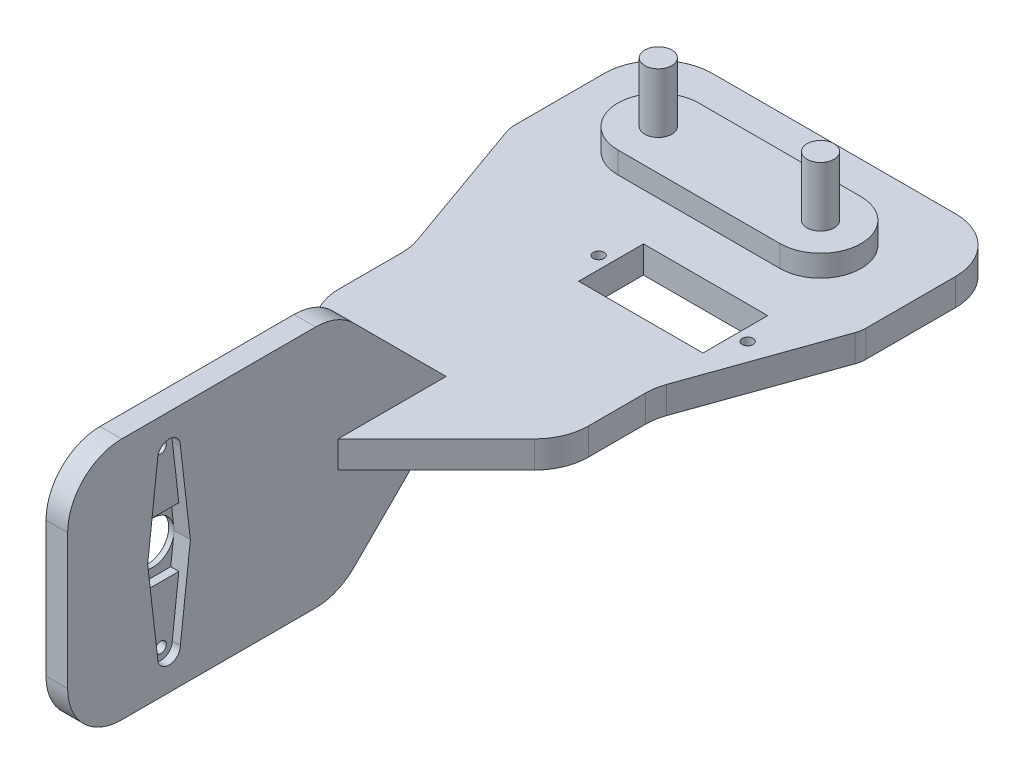
SolidWorks part; units mm, degrees
note: The reader was unsure of these and kept them because the rebuilt part matched: shared geometry of "Sketch1<3>", "Sketch1<4>", "Sketch8<3>", "Sketch8<4>".
ref_plane "Front Plane" through (0, 0, 0) normal (0, 0, 1) x (1, 0, 0)
ref_plane "Top Plane" through (0, 0, 0) normal (0, 1, 0) x (1, 0, 0)
ref_plane "Right Plane" through (0, 0, 0) normal (1, 0, 0) x (0, 0, -1)
sketch "Sketch1" plane through (0, 0, 0) normal (0, 1, 0) x (1, 0, 0)
  line L0 (15.5811, 10.6625) -> (15.5811, -11.8375) construction
  line L2 (-31.9189, 1.554) -> (-31.9189, 18.1625)
  line L3 (-21.9189, 28.1625) -> (23.0811, 28.1625)
  line L5 (10.4961, -17.4925) -> (10.4961, -5.5125) construction
  line L6 (-21.9189, -64.9925) -> (23.0811, -64.9925)
  line L7 (-0.9939, -17.4925) -> (21.9861, -17.4925)
  line L8 (-0.9939, -17.4925) -> (-0.9939, -5.5125)
  line L9 (-0.9939, -5.5125) -> (21.9861, -5.5125)
  line L11 (23.0811, -27.4925) -> (23.0811, -64.9925)
  line L17 (15.5811, 18.1625) -> (-14.4189, 18.1625)
  line L18 (-14.4189, 3.1625) -> (15.5811, 3.1625)
  line L19 (-31.6205, -0.1776) -> (-21.9189, -27.4925)
  line L23 (32.7828, -0.1776) -> (23.0811, -27.4925)
  line L24 (21.9861, -17.4925) -> (21.9861, -5.5125)
  line L25 (33.0811, 1.554) -> (33.0811, 18.1625)
  line L26 (-21.9189, -27.4925) -> (-21.9189, -64.9925)
  circle A1 centre (-3.2839, -11.5025) radius 1
  circle A3 centre (15.5811, -11.8375) radius 2.525 construction
  arc A4 (-14.4189, 18.1625) -> (-14.4189, 3.1625) centre (-14.4189, 10.6625) ccw
  circle A5 centre (-14.4189, 10.6625) radius 2.5
  arc A6 (-31.9189, 18.1625) -> (-21.9189, 28.1625) centre (-21.9189, 18.1625) cw
  arc A8 (-31.6205, -0.1776) -> (-31.9189, 1.554) centre (-26.7453, 1.554) cw
  arc A9 (32.7828, -0.1776) -> (33.0811, 1.554) centre (27.9076, 1.554) ccw
  arc A11 (33.0811, 18.1625) -> (23.0811, 28.1625) centre (23.0811, 18.1625) ccw
  circle A12 centre (15.5811, 10.6625) radius 2.5
  arc A13 (15.5811, 18.1625) -> (15.5811, 3.1625) centre (15.5811, 10.6625) cw
  circle A15 centre (15.5811, -11.8375) radius 7.5 construction
  circle A17 centre (24.2761, -11.5025) radius 1
  point P0 (0, 0)
  point P1 (32.5, 0.6625)
  point P7 (10.4961, -17.4925)
  point P17 (10.4961, -5.5125)
  point P24 (0.5811, 18.1625)
  point P37 (-31.9189, 0.6625)
  point P46 (21.9861, -11.5025)
  point P56 (0.5811, 3.1625)
  dimension "D7" = 2
  dimension "D10" = 5.05
  dimension "D6" = 5
  dimension "D8" = 5
  dimension "D19" = 10
  dimension "D20" = 8.675
  dimension "D15" = 15
  dimension "D16" = 5.1735
  dimension "D12" = 6.405
  dimension "D18" = 6.405
  dimension "D3" = 10
  dimension "D4" = 11.49
  dimension "D5" = 10
  dimension "D9" = 2.29
  dimension "D11" = 37.5
  dimension "D13" = 22.5
  dimension "D14" = 10
  dimension "D17" = 11.98
  dimension "D21" = 17.5
  dimension "D22" = 65
  dimension "D23" = 30
  dimension "D24" = 45
extrude "Boss-Extrude1" add sketch "Sketch1" along normal blind 5
extrude "Boss-Extrude2" add sketch "Sketch1<3>" along normal blind 9 contours A13 L17 A4 L18 A5 A12
sketch "Sketch1<3>" plane through (0, 0, 0) normal (0, 1, 0) x (1, 0, 0) same geometry as "Sketch1"
extrude "Boss-Extrude3" add sketch "Sketch1<4>" along normal blind 20 contours A12 | A5
sketch "Sketch1<4>" plane through (0, 0, 0) normal (0, 1, 0) x (1, 0, 0) same geometry as "Sketch1"
sketch "Sketch2" plane through (0, 0, 64.9925) normal (0, 0, 1) x (1, 0, 0)
  line L1 (-2, 25) -> (2, 25)
  line L2 (-2, 25) -> (-2, -20)
  line L3 (-2, -20) -> (2, -20)
  line L4 (2, 25) -> (2, -20)
  line L5 (-2, 25) -> (2, -20) construction
  line L6 (-2, -20) -> (2, 25) construction
  line L7 (-21.9189, 0) -> (23.0811, 0) construction
  point P0 (0, 2.5)
  dimension "D1" = 2.5
  dimension "D2" = 45
  dimension "D3" = 4
ref_plane "Plane1" through (0.5811, 0, 0) normal (-1, 0, 0) x (0, 0, 1)
ref_plane "Plane2" through (0, 2.5, 0) normal (0, 1, 0) x (1, 0, 0)
extrude "Boss-Extrude4" add sketch "Sketch2" along normal blind 50 contours L4 L3 L2 L1
sketch "Sketch6" plane through (0, 5, 0) normal (0, 1, 0) x (1, 0, 0)
  line L0 (-2, -64.9925) -> (-21.9189, -45.0736)
  line L1 (-21.9189, -27.4925) -> (-21.9189, -64.9925) construction
  line L2 (-21.9189, -64.9925) -> (-2, -64.9925) construction
  line L3 (-21.9189, -45.0736) -> (-21.9189, -64.9925)
  line L4 (-21.9189, -64.9925) -> (-2, -64.9925)
  line L5 (2, -64.9925) -> (23.0811, -43.9114)
  line L6 (23.0811, -27.4925) -> (23.0811, -64.9925) construction
  line L7 (2, -64.9925) -> (23.0811, -64.9925) construction
  line L8 (23.0811, -43.9114) -> (23.0811, -64.9925)
  line L9 (23.0811, -64.9925) -> (2, -64.9925)
  dimension "D1" = 45
  dimension "D2" = 45
extrude "Cut-Extrude1" cut sketch "Sketch6" against normal through all
ref_plane "Plane3" through (0, 0, 0) normal (1, 0, 0) x (0, 0, -1)
sketch "Sketch7" plane through (0, 0, 0) normal (1, 0, 0) x (0, 0, -1)
  line L0 (-64.9925, 25) -> (-44.9925, 5)
  line L1 (-64.9925, 25) -> (-64.9925, 5) construction
  line L2 (-64.9925, 5) -> (-45.0736, 5) construction
  dimension "D1" = 45
rib "Rib8" sketch "Sketch7" sketch "Sketch7" thickness 4 extrusion direction parallel to sketch draft on no parameters "D1"=4
mirror "Mirror2" about plane through (0, 2.5, 0) normal (0, 1, 0) of "Rib8"
sketch "Sketch8" plane through (2, 0, 0) normal (1, 0, 0) x (0, 0, -1)
  line L0 (35.75, 2.5) -> (-35.75, 2.5) construction
  line L1 (-98.3425, 18.5) -> (-100.1925, 2.5)
  line L2 (-94.1425, 18.5) -> (-92.2925, 2.5)
  line L3 (-114.9925, 25) -> (-114.9925, -20) construction
  line L4 (-64.9925, 5) -> (-64.9925, 0) construction
  line L5 (-98.3425, -13.5) -> (-100.1925, 2.5)
  line L6 (-94.1425, -13.5) -> (-92.2925, 2.5)
  line L7 (-99.5566, 8) -> (-92.9284, 8)
  line L8 (-99.5566, -3) -> (-92.9284, -3)
  arc A0 (-100.0883, 3.4014) -> (-100.0883, 1.5986) centre (-96.2425, 2.5) ccw
  arc A1 (-94.1425, 18.5) -> (-98.3425, 18.5) centre (-96.2425, 18.5) ccw
  circle A2 centre (-96.2425, 18.5) radius 1
  arc A3 (-94.1425, -13.5) -> (-98.3425, -13.5) centre (-96.2425, -13.5) cw
  circle A4 centre (-96.2425, -13.5) radius 1
  arc A5 (-92.3967, 1.5986) -> (-92.3967, 3.4014) centre (-96.2425, 2.5) ccw
  dimension "D1" = 7.9
  dimension "D2" = 4.2
  dimension "D6" = 2
  dimension "D3" = 32
  dimension "D4" = 18.75
  dimension "D5" = 50
  dimension "D7" = 11
  dimension "D8" = 5.5
extrude "Cut-Extrude2" cut sketch "Sketch8" against normal blind 3 contours A3 L6 L2 A1 L1 L5 A2 A4
extrude "Cut-Extrude3" cut sketch "Sketch8<3>" against normal through all contours A2 | A4
sketch "Sketch8<3>" plane through (2, 0, 0) normal (1, 0, 0) x (0, 0, -1) same geometry as "Sketch8"
fillet "Fillet1" radius 10 8 edges at (0, -20, 114.9925) (0, -20, 64.9925) (0, 25, 114.9925) (0, 25, 64.9925) (-21.9189, 2.5, 27.4925) (-21.9189, 2.5, 45.0736) (23.0811, 2.5, 27.4925) (23.0811, 2.5, 43.9114)
extrude "Cut-Extrude4" cut sketch "Sketch8<4>" against normal blind 1.5 contours L2 A1 L1 L7 A2 | A3 L6 L8 L5 A4
sketch "Sketch8<4>" plane through (2, 0, 0) normal (1, 0, 0) x (0, 0, -1) same geometry as "Sketch8"
sketch "Sketch9" plane through (-1, 0, 0) normal (1, 0, 0) x (0, 0, -1)
  line L0 (-99.5566, 8) -> (-92.9284, 8) construction
  circle A0 centre (-96.2425, 2.5) radius 3.95
  point P3 (0, 0)
  point P8 (-96.2425, 8)
extrude "Cut-Extrude5" cut sketch "Sketch9" against normal blind 10 contours A0
